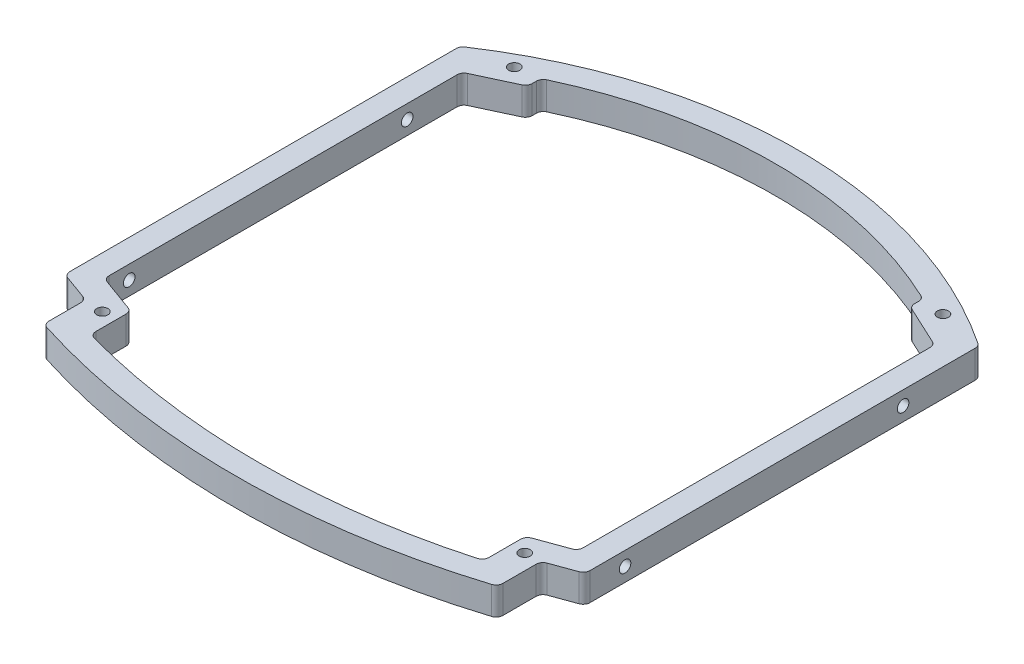
SolidWorks part; units mm, degrees
ref_plane "Front Plane" through (0, 0, 0) normal (0, 0, 1) x (1, 0, 0)
ref_plane "Top Plane" through (0, 0, 0) normal (0, 1, 0) x (1, 0, 0)
ref_plane "Right Plane" through (0, 0, 0) normal (1, 0, 0) x (0, 0, -1)
sketch "Sketch1" plane through (0, 0, 0) normal (0, 1, 0) x (1, 0, 0)
  line L0 (-56, -47.2105) -> (-56, 38)
  line L1 (56, -46.9471) -> (56, 38)
  line L2 (-51, -43.7095) -> (-51, 33.3715)
  line L3 (51, 33.4249) -> (51, -43.446)
  line L4 (-56, -47.2105) -> (-49, -49.7583)
  line L5 (-49, -49.7583) -> (-49, -58.7807)
  line L6 (49, -58.7807) -> (49, -49.4949)
  line L7 (49, -49.4949) -> (56, -46.9471)
  line L10 (-51, -43.7095) -> (-42, -46.9852)
  line L11 (-50, 44.85) -> (50, 44.85) construction
  line L12 (-50, 44.85) -> (-50, -55.15) construction
  line L13 (-50, -55.15) -> (50, -55.15) construction
  line L14 (50, 44.85) -> (50, -55.15) construction
  line L15 (-42, -46.9852) -> (-42, -55.6697)
  line L16 (42.65, -55.4852) -> (42.65, -46.4852)
  line L17 (42.65, -46.4852) -> (51, -43.446)
  line L18 (41.15, 40.776) -> (41.15, 38.018)
  line L19 (41.15, 38.018) -> (51, 33.4249)
  line L20 (-51, 33.3715) -> (-41.25, 37.918)
  line L21 (-41.25, 37.918) -> (-41.25, 40.7278)
  arc A0 (-56, 38) -> (56, 38) centre (0, -44.8493) cw
  arc A1 (-49, -58.7807) -> (49, -58.7807) centre (0, 93.5315) ccw
  arc A2 (-41.25, 40.7278) -> (41.15, 40.776) centre (0, -44.8493) cw
  arc A3 (42.65, -55.4852) -> (-42, -55.6697) centre (0, 93.5315) cw
  circle A4 centre (-46.25, 40) radius 1.2
  circle A5 centre (46.15, 40.1) radius 1.2
  circle A6 centre (45.65, -49.65) radius 1.2
  circle A7 centre (-45, -50.15) radius 1.2
  point P7 (0, 0)
  dimension "D11" = 100
  dimension "D7" = 160
  dimension "D9" = 2.4
  dimension "D19" = 5
  dimension "D36" = 5
  dimension "D5" = 7
  dimension "D3" = 56
  dimension "D6" = 100
  dimension "D4" = 5
  dimension "D8" = 50
  dimension "D10" = 5
  dimension "D12" = 5
  dimension "D13" = 3.75
  dimension "D14" = 4.85
  dimension "D15" = 3.85
  dimension "D16" = 4.75
  dimension "D17" = 5.5
  dimension "D18" = 4.35
  dimension "D20" = 4
  dimension "D21" = 3
  dimension "D22" = 110
  dimension "D23" = 3
  dimension "D24" = 4
  dimension "D25" = 110
  dimension "D26" = 4
  dimension "D27" = 5
  dimension "D28" = 115
  dimension "D29" = 5
  dimension "D30" = 4
  dimension "D31" = 115
  dimension "D32" = 40
  dimension "D33" = 5
  dimension "D34" = 2
  dimension "D35" = 7
  dimension "D37" = 5
  dimension "D38" = 5
  dimension "D39" = 9
  dimension "D40" = 112
extrude "Boss-Extrude1" add sketch "Sketch1" along normal blind 6
hole_wizard "Tap Drill for M3 Tap1" positions "Sketch3" profile "Sketch2" hole size "M3" standard "ISO"
sketch "Sketch3" plane through (-56, 0, 0) normal (-1, 0, 0) x (0, 0, 1)
  line L0 (-38, 0) -> (47.2105, 0) construction
  line L1 (56.3484, 6) -> (56.3484, 0) construction
  point P0 (-21.6516, 3)
  point P2 (38.3484, 3)
  dimension "D1" = 3
  dimension "D2" = 3
  dimension "D3" = 60
  dimension "D4" = 18
sketch "Sketch2" plane through (-56, 3, -21.6516) normal (0, 1, 0) x (0, 0, 1)
  line L0 (0, 0) -> (0, 10.7511)
  line L1 (0, 10.7511) -> (1.25, 10)
  line L2 (1.25, 10) -> (1.25, 0)
  line L5 (1.25, 0) -> (0, 0)
  line L10 (0, 10.7511) -> (-1.25, 10) construction
  line L11 (0, -6.35) -> (0, 107.95) construction
  dimension "Hole Dia." = 2.5
  dimension "Hole Depth" = 10
  dimension "Drill Angle" = 118
mirror "Mirror1" about plane through (0, 0, 0) normal (1, 0, 0) of "Tap Drill for M3 Tap1"
fillet "Fillet1" radius 1.5 20 edges at (56, 3, -38) (-56, 3, -38) (-56, 3, 47.2105) (49, 3, 49.4949) (56, 3, 46.9471) (49, 3, 58.7807) (-49, 3, 58.7807) (-49, 3, 49.7583) (-42, 3, 55.6697) (-42, 3, 46.9852) (-51, 3, 43.7095) (42.65, 3, 55.4852) (42.65, 3, 46.4852) (51, 3, 43.446) (51, 3, -33.4249) (41.15, 3, -38.018) (41.15, 3, -40.776) (-51, 3, -33.3715) (-41.25, 3, -40.7278) (-41.25, 3, -37.918)
